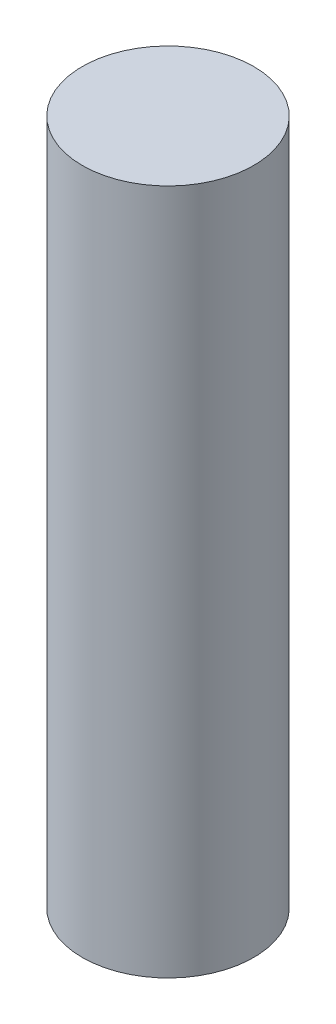
SolidWorks part; units mm, degrees
ref_plane "Front Plane" through (0, 0, 0) normal (0, 0, 1) x (1, 0, 0)
ref_plane "Top Plane" through (0, 0, 0) normal (0, 1, 0) x (1, 0, 0)
ref_plane "Right Plane" through (0, 0, 0) normal (1, 0, 0) x (0, 0, -1)
sketch "Sketch1" plane through (0, 76.2, 0) normal (0, 1, 0) x (1, 0, 0)
  line L0 (44.45, 0) -> (44.45, -88.9) construction
  line L1 (0, 0) -> (88.9, 0) construction
  line L2 (0, -88.9) -> (88.9, -88.9) construction
  circle A0 centre (44.45, -44.45) radius 9.525
  dimension "D1" = 19.05
extrude "Boss-Extrude1" add sketch "Sketch1" along normal blind 38.1 and the other way blind 38.1 contours A0
